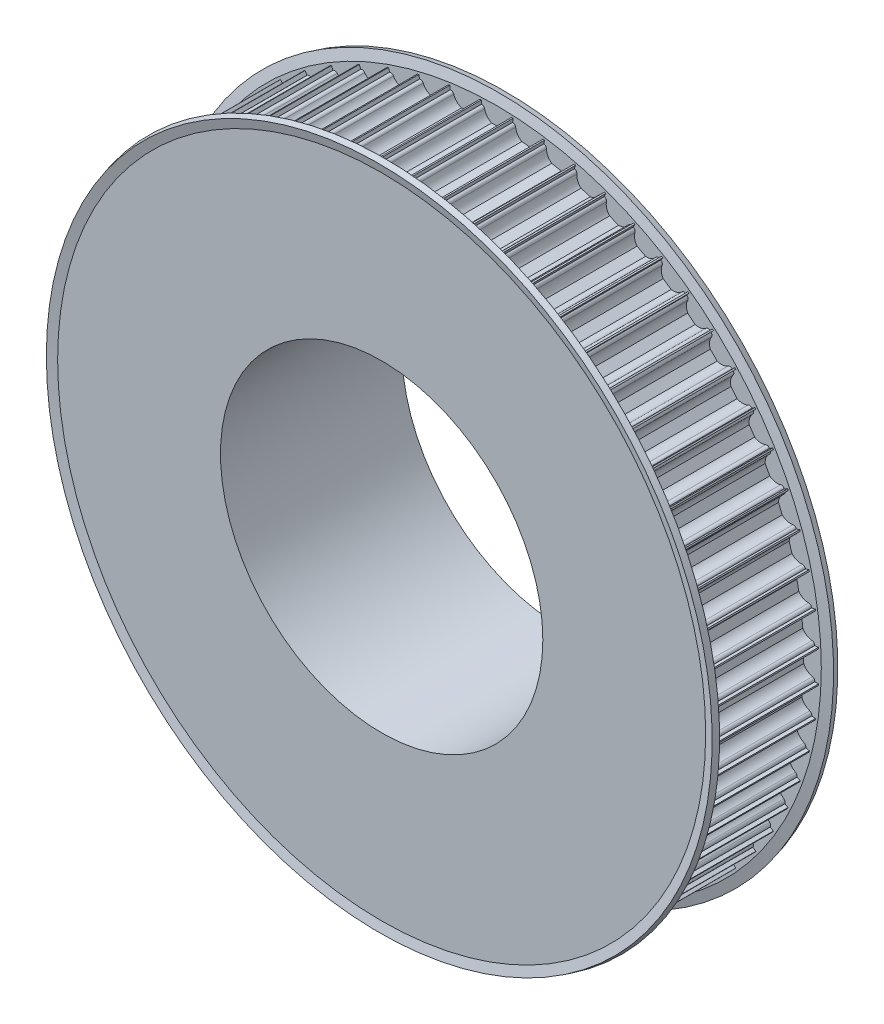
SolidWorks part; units mm, degrees
ref_plane "Front Plane" through (0, 0, 0) normal (0, 0, 1) x (1, 0, 0)
ref_plane "Top Plane" through (0, 0, 0) normal (0, 1, 0) x (1, 0, 0)
ref_plane "Right Plane" through (0, 0, 0) normal (1, 0, 0) x (0, 0, -1)
sketch "Sketch2" plane through (0, 0, 0) normal (1, 0, 0) x (0, 0, -1)
  line L0 (0, 0) -> (89.4717, 0) construction
  line L1 (0, 40) -> (0, 80)
  line L2 (0, 80) -> (30, 80)
  line L3 (30, 80) -> (30, 55.5)
  line L4 (30, 55.5) -> (45, 55.5)
  line L5 (45, 55.5) -> (45, 40)
  line L6 (45, 40) -> (0, 40)
  dimension "D1" = 80
  dimension "D2" = 40
  dimension "D3" = 30
  dimension "D4" = 15
  dimension "D5" = 15.5
revolve "Revolve1" add sketch "Sketch2" angle 360 about L0
sketch "Sketch3" plane through (0, 0, 0) normal (0, 0, 1) x (1, 0, 0)
  line L0 (-3.6742, 79) -> (-3.75, 79)
  line L1 (-3.75, 79) -> (-3.75, 81)
  line L2 (-3.75, 81) -> (3.75, 81)
  line L3 (3.75, 81) -> (3.75, 79)
  line L4 (3.75, 79) -> (3.6742, 79)
  line L5 (-1.199, 76.25) -> (1.199, 76.25)
  arc A0 (2.9394, 78.4) -> (1.199, 76.25) centre (0, 79) cw
  arc A1 (2.9394, 78.4) -> (3.6742, 79) centre (3.6742, 78.25) cw
  arc A2 (-2.9394, 78.4) -> (-3.6742, 79) centre (-3.6742, 78.25) ccw
  arc A3 (-1.199, 76.25) -> (-2.9394, 78.4) centre (0, 79) cw
  point P9 (0, 81)
  dimension "D2" = 3
  dimension "D6" = 0.75
  dimension "D1" = 79
  dimension "D3" = 2
  dimension "D4" = 7.5
  dimension "D5" = 2.75
extrude "Cut-Extrude1" cut sketch "Sketch3" against normal up to next
pattern_circular "CirPattern1" count 64 over 360 about axis through (0, 0, 0) along (0, 0, 1) of "Cut-Extrude1"
sketch "Sketch4" plane through (0, 0, 0) normal (1, 0, 0) x (0, 0, -1)
  line L0 (15, -40.9775) -> (15, -4.0868) construction
  line L1 (30, -40.9775) -> (0, -40.9775) construction
  line L2 (30, -4.0868) -> (0, -4.0868) construction
  line L3 (30, 55.5) -> (30, 80.4125)
  line L4 (30, 80.4125) -> (30.592, 82.6218)
  line L5 (30.592, 82.6218) -> (29.1431, 83.01)
  line L6 (29.1431, 83.01) -> (28.5, 80.61)
  line L7 (28.5, 80.61) -> (28.5, 55.5)
  line L8 (28.5, 55.5) -> (30, 55.5)
  line L9 (1.5, 55.5) -> (0, 55.5)
  line L10 (1.5, 80.61) -> (1.5, 55.5)
  line L11 (0, 55.5) -> (0, 80.4125)
  line L12 (-0.592, 82.6218) -> (0.8569, 83.01)
  line L13 (0, 80.4125) -> (-0.592, 82.6218)
  line L14 (0.8569, 83.01) -> (1.5, 80.61)
  line L15 (0, 0) -> (-34.5262, 0) construction
  dimension "D1" = 1.5
  dimension "D2" = 25.11
  dimension "D3" = 2.4
  dimension "D4" = 15
revolve "Revolve2" add sketch "Sketch4" angle 360 about L15
